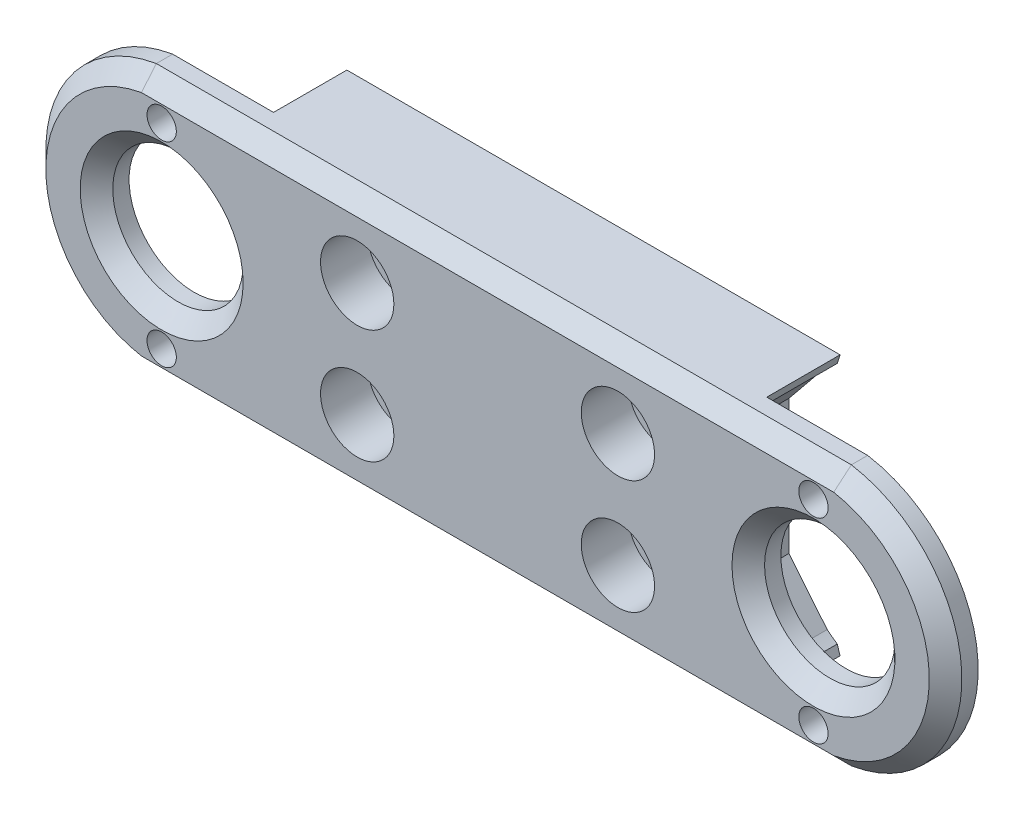
SolidWorks part; units mm, degrees
ref_plane "Alzado" through (0, 0, 0) normal (0, 0, 1) x (1, 0, 0)
ref_plane "Planta" through (0, 0, 0) normal (0, 1, 0) x (1, 0, 0)
ref_plane "Vista lateral" through (0, 0, 0) normal (1, 0, 0) x (0, 0, -1)
sketch "Croquis1" plane through (0, 0, 0) normal (0, 0, 1) x (1, 0, 0)
  line L0 (0, 0) -> (7143.243, 0) construction
  line L1 (0, 0) -> (0, 7143.243) construction
  line L3 (-1.3266, 8) -> (20, 8)
  line L4 (20, 8) -> (20, 0)
  line L5 (20, 0) -> (8, 0)
  line L6 (8, 0) -> (8, 4.1231) construction
  line L8 (10.8753, 7) -> (-12.9398, 7) construction
  line L9 (5.6569, 7) -> (8, 4.1231) construction
  line L10 (-8.1093, 0) -> (8, 0)
  circle A0 centre (0, 6) radius 0.9
  circle A2 centre (12, 3.5) radius 1.1
  circle A3 centre (0, 0) radius 9 construction
  arc A4 (-1.3266, 8) -> (-8.1093, 0) centre (0, 0) ccw
  dimension "D1" = 6
  dimension "1,8" = 1.8
  dimension "D5" = 7
  dimension "2,2" = 2.2
  dimension "D7" = 18
  dimension "D3" = 8
  dimension "D6" = 12
  dimension "8" = 8
  dimension "D8" = 7
  dimension "D9" = 20
extrude "Saliente-Extruir1" add sketch "Croquis1" along normal blind 6.5
sketch "Croquis4" plane through (0, 0, 0) normal (0, 0, -1) x (-1, 0, 0)
  line L2 (-5.6569, 7) -> (-8, 4.1231)
  line L3 (-8, 4.1231) -> (-8, 0)
  line L4 (-8, 0) -> (8.1093, 0)
  line L7 (200000, 0) -> (-207143.243, 0) construction
  line L8 (8.1093, 0) -> (9, 0)
  arc A2 (-5.6569, 7) -> (9, 0) centre (0, 0) cw
extrude "Cortar-Extruir6" cut sketch "Croquis4" along direction (0, 0, 1) on the side against the normal offset from surface (4.5 mm away) 2
chamfer "Chaflán1" distance 1 angle 45 3 edges at (-6.1854, 5.2441, 6.5) (9.3367, 8, 6.5) (4.1231, 8, 2.25)
sketch "Croquis5" plane through (0, 0, 0) normal (0, 0, -1) x (-1, 0, 0)
  line L0 (-8, 0) -> (-8, 4.1231) construction
  line L1 (-20, 0) -> (-8, 0)
  line L2 (-20, 0) -> (-20, 2.5)
  line L3 (-20, 2.5) -> (-8, 2.5)
  line L4 (-8, 0) -> (-8, 2.5)
  line L5 (-20, 0) -> (-8, 2.5) construction
  line L6 (-20, 2.5) -> (-8, 0) construction
  point P4 (-14, 1.25)
  dimension "D1" = 2.5
extrude "Cortar-Extruir7" cut sketch "Croquis5" against normal offset from surface (3 mm away) 1.5 up to face at (0.9, 6, 4.5)
sketch "Croquis6" plane through (0, 0, 6.5) normal (0, 0, 1) x (1, 0, 0)
  circle A0 centre (12, 3.5) radius 2.25
  dimension "D1" = 4.5
extrude "Cortar-Extruir8" cut sketch "Croquis6" against normal offset from surface (2.9 mm away) 0.6 up to face at (13.3333, 1.65, 3)
chamfer "Chaflán3" distance 0.2 angle 45 1 edges at (0.9, 6, 4.5)
mirror "Simetría1" about plane through (20, 0, 6.5) normal (0, 1, 0) of bodies 108 101
sketch "Croquis7" plane through (0, 0, 6.5) normal (0, 0, 1) x (1, 0, 0)
  circle A0 centre (0, 0) radius 4
  dimension "D1" = 8
extrude "Cortar-Extruir9" cut sketch "Croquis7" against normal through all
chamfer "Chaflán2" distance 1 angle 45 1 edges at (4, 0, 6.5)
mirror "Simetría2" about plane through (20, 8, 6.5) normal (-1, 0, 0) of bodies 109 102
sketch "Croquis3" plane through (0, 0, 6.5) normal (0, 0, 1) x (1, 0, 0)
  line L1 (17, -16.5246) -> (23, -16.5246)
  line L2 (17, -16.5246) -> (17, 0.5246)
  line L3 (17, 0.5246) -> (23, 0.5246)
  line L4 (23, -16.5246) -> (23, 0.5246)
  line L5 (17, -16.5246) -> (23, 0.5246) construction
  line L6 (17, 0.5246) -> (23, -16.5246) construction
  line L8 (-1.3266, -8) -> (41.3266, -8) construction
  point P0 (20, -8)
  point P5 (20.026, -8.1053)
  point P6 (20, -8)
  point P9 (23, 0.5246)
  dimension "D1" = 6
  dimension "D2" = 17.0493
extrude "Cortar-Extruir2" cut sketch "Croquis3" against normal through all from surface
sketch "Croquis8" plane through (0, 0, 0) normal (0, 0, -1) x (-1, 0, 0)
  line L1 (-25.1799, 6.9593) -> (-14.8201, 6.9593)
  line L2 (-25.1799, 6.9593) -> (-25.1799, -6.9593)
  line L3 (-25.1799, -6.9593) -> (-14.8201, -6.9593)
  line L4 (-14.8201, 6.9593) -> (-14.8201, -6.9593)
  line L5 (-25.1799, 6.9593) -> (-14.8201, -6.9593) construction
  line L6 (-25.1799, -6.9593) -> (-14.8201, 6.9593) construction
  point P0 (-20, 0)
extrude "Cortar-Extruir10" cut sketch "Croquis8" against normal offset from surface (5.5 mm away) 1 up to face at (5, 0, 6.5)
